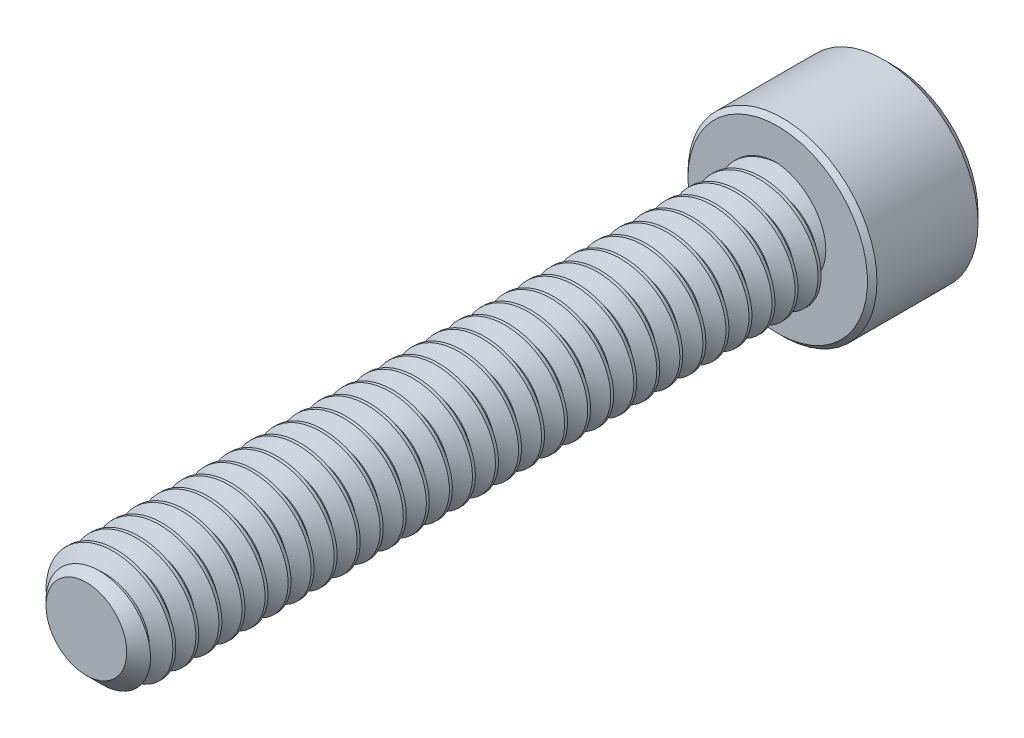
SolidWorks part; units mm, degrees
ref_plane "Front Plane" through (0, 0, 0) normal (0, 0, 1) x (1, 0, 0)
ref_plane "Top Plane" through (0, 0, 0) normal (0, 1, 0) x (1, 0, 0)
ref_plane "Right Plane" through (0, 0, 0) normal (1, 0, 0) x (0, 0, -1)
sketch "Sketch0" plane through (0, 0, 0) normal (1, 0, 0) x (0, 0, -1)
  line L0 (0, 0) -> (19.05, 0) construction
  point P2 (22.225, 0)
  point P4 (0, 0)
  dimension "D1" = 19.05
  dimension "D2" = 3.175
  dimension "Min Thread" = 0
sketch "Sketch1" plane through (0, 0, 0) normal (0, 0, 1) x (1, 0, 0)
  circle A0 centre (0, 0) radius 1.5875
  dimension "OD" = 3.175
extrude "Extrude1" add sketch "Sketch1" against normal blind 19.05
sketch "Sketch2" plane through (0, 0, 0) normal (0, 0, 1) x (1, 0, 0)
  circle A0 centre (0, 0) radius 1.5875 construction
  circle A1 centre (0, 0) radius 1.5875
curve "Helix/Spiral1" pitch 0.635 height 19.685 turns 31 parameters "pitch"=0.635
chamfer "Chamfer3" distance 0.4763 angle 45 1 edges at (1.5875, 0, 0)
sketch "Sketch3" plane through (0, 0, 0) normal (1, 0, 0) x (0, 0, -1)
  line L0 (-0.5556, 1.5875) -> (-0.3175, 1.1751)
  line L1 (-0.3175, 1.1751) -> (-0.2381, 1.1751)
  line L2 (-0.2381, 1.1751) -> (0, 1.5875)
  line L3 (-0.5556, 1.5875) -> (0, 1.5875)
  line L4 (-0.2778, 1.5875) -> (-0.2778, 1.1751) construction
  line L5 (-0.4366, 1.3813) -> (-0.1191, 1.3813) construction
  line L6 (0, 1.5875) -> (0, -1.5875) construction
  dimension "D1" = 0.0794
  dimension "D2" = 0.3175
  dimension "D3" = 60
sweep "Cut-Sweep1" cut profiles "Sketch3" path "Helix/Spiral1"
sketch "Sketch5" plane through (0, 0, 0) normal (1, 0, 0) x (0, 0, -1)
  line L0 (19.05, -1.1864) -> (19.05, 1.1327) construction
  line L1 (19.05, 1.5875) -> (0, 1.5875)
  line L2 (19.05, 1.5875) -> (19.05, 0)
  line L3 (19.05, 0) -> (-0.5778, 0)
  line L4 (0, 0) -> (19.05, 0) construction
  line L5 (0, 1.5875) -> (-0.5778, 0)
  line L6 (0, 0) -> (21.59, 0) construction
  dimension "D1" = 70
  dimension "D3" = 2.54
revolve "partially thread" [suppressed] add sketch "Sketch5" angle 360 about L6
sketch "Sketch6" plane through (0, 0, -19.05) normal (0, 0, -1) x (-1, 0, 0)
  circle A0 centre (0, 0) radius 2.6035
  dimension "head dia" = 5.207
extrude "Extrude2" add sketch "Sketch6" along normal blind 3.175
sketch "Sketch7" plane through (0, 0, -22.225) normal (0, 0, -1) x (-1, 0, 0)
  line L1 (0, 1.3748) -> (-1.1906, 0.6874)
  line L2 (-1.1906, 0.6874) -> (-1.1906, -0.6874)
  line L3 (-1.1906, -0.6874) -> (0, -1.3748)
  line L4 (0, -1.3748) -> (1.1906, -0.6874)
  line L5 (1.1906, -0.6874) -> (1.1906, 0.6874)
  line L6 (1.1906, 0.6874) -> (0, 1.3748)
  circle A0 centre (0, 0) radius 1.1906 construction
  dimension "hex dia" = 2.3813
extrude "Cut-Extrude1" cut sketch "Sketch7" against normal blind 1.7859
sketch "Sketch8" plane through (0, 0, -22.225) normal (0, 0, -1) x (-1, 0, 0)
  circle A0 centre (0, 0) radius 1.3748
extrude "Cut-Extrude2" cut sketch "Sketch8" against normal through all draft 45
chamfer "Chamfer1" distance 0.2604 angle 45 1 edges at (-2.6035, 0, -22.225)
chamfer "Chamfer2" distance 0.1302 angle 45 1 edges at (-2.6035, 0, -19.05)
sketch "Sketch9" plane through (0, 0, 0) normal (1, 0, 0) x (0, 0, -1)
  line L0 (0, 1.5875) -> (0, -1.5875) construction
  line L1 (1.5875, 1.5875) -> (1.5875, -1.5875) construction
  line L2 (22.225, 2.6035) -> (22.225, -2.6035) construction
  line L3 (19.05, 2.6035) -> (19.05, -2.6035) construction
  line L4 (19.05, 2.4733) -> (19.05, -2.4733) construction
  line L5 (22.225, -2.3431) -> (22.225, 2.3431) construction
  line L6 (19.05, -2.6035) -> (19.05, 2.6035) construction
  line L7 (0, 1.1113) -> (0, -1.1113) construction
  line L8 (-0.5556, 1.5875) -> (0, 1.5875) construction
  line L9 (1.5875, 0) -> (0, 0) construction
  dimension "D1" = 1.5875
equation "\"D3@Helix/Spiral1\" = \"screw length@Extrude1\"+\"pitch@Helix/Spiral1\""
equation "\"D1@Sketch3\" = \"pitch@Helix/Spiral1\"*.125"
equation "\"D2@Sketch3\" = \"pitch@Helix/Spiral1\"*.5"
equation "\"D1@Cut-Extrude1\" = \"hex dia@Sketch7\"*.75"
equation "\"D1@Chamfer1\" = \"head dia@Sketch6\"*.05"
equation "\"D1@Sketch9\" = \"pitch@Helix/Spiral1\"*2.50"
equation "\"D1@Chamfer2\" = \"D1@Chamfer1\"/2"
equation "\"D1@Chamfer3\" = \"pitch@Helix/Spiral1\"*.750"
equation "\"D1@Sketch0\" = \"screw length@Extrude1\""
equation "\"D2@Sketch0\" = \"head depth@Extrude2\""
